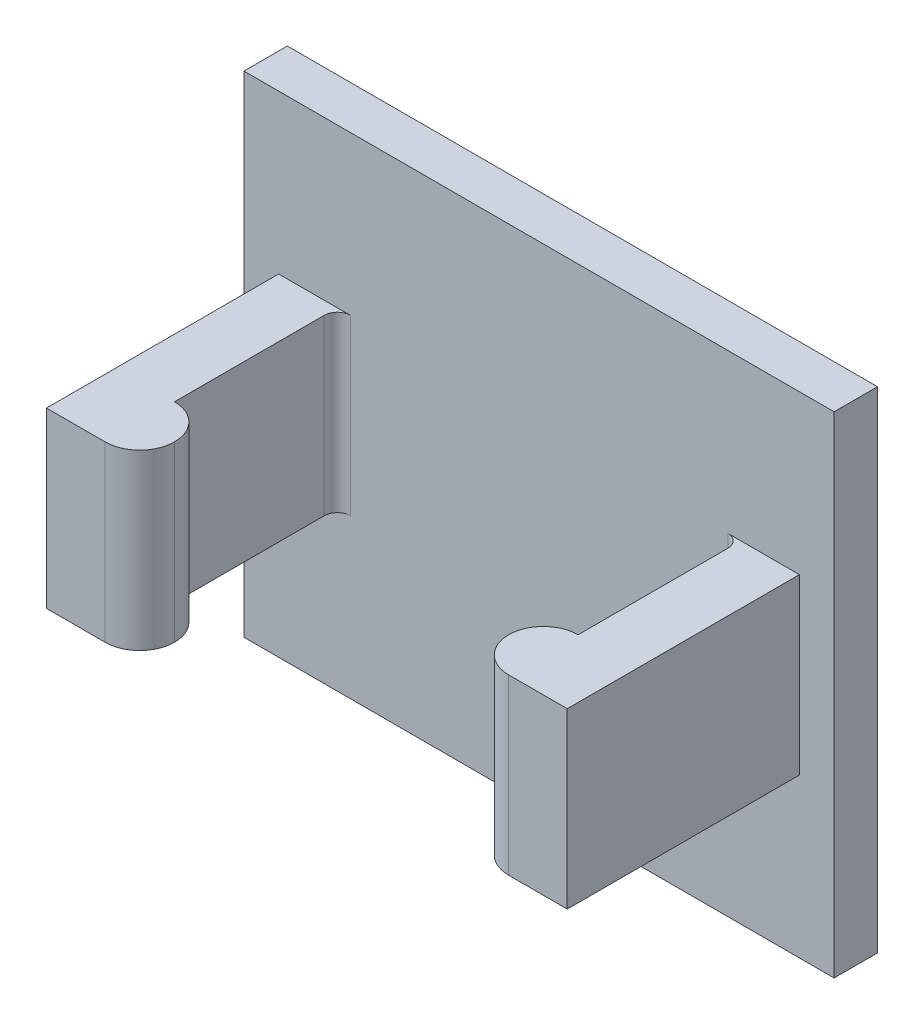
SolidWorks part; units mm, degrees
ref_plane "정면" through (0, 0, 0) normal (0, 0, 1) x (1, 0, 0)
ref_plane "윗면" through (0, 0, 0) normal (0, 1, 0) x (1, 0, 0)
ref_plane "우측면" through (0, 0, 0) normal (1, 0, 0) x (0, 0, -1)
sketch "스케치1" plane through (0, 0, 0) normal (0, 0, 1) x (1, 0, 0)
  line L1 (-6, -5.65) -> (6, -5.65)
  line L2 (-6, -5.65) -> (-6, 5.65)
  line L3 (-6, 5.65) -> (6, 5.65)
  line L4 (6, -5.65) -> (6, 5.65)
  line L5 (-6, -5.65) -> (6, 5.65) construction
  line L6 (-6, 5.65) -> (6, -5.65) construction
  point P0 (0, 0)
  dimension "D1" = 12
  dimension "D2" = 11.3
extrude "보스-돌출1" add sketch "스케치1" along normal blind 1
sketch "스케치2" plane through (0, 0, 1) normal (0, 0, 1) x (1, 0, 0)
  line L0 (-6, 5.65) -> (-6, -5.65) construction
  line L1 (-6, 2) -> (-4.65, 2)
  line L2 (-6, 2) -> (-6, -2)
  line L3 (-6, -2) -> (-4.65, -2)
  line L4 (-4.65, 2) -> (-4.65, -2)
  line L5 (6, -5.65) -> (6, 5.65) construction
  line L6 (6, 2) -> (4.65, 2)
  line L7 (6, 2) -> (6, -2)
  line L8 (6, -2) -> (4.65, -2)
  line L9 (4.65, 2) -> (4.65, -2)
  point P12 (-4.65, 0)
  point P14 (6, 0)
  dimension "D1" = 1.35
  dimension "D2" = 1.35
  dimension "D3" = 4
  dimension "D4" = 4
  dimension "D5" = 0
  dimension "D6" = 0
extrude "보스-돌출2" add sketch "스케치2" along normal blind 5.35
sketch "스케치3" plane through (-4.65, 0, 0) normal (1, 0, 0) x (0, 0, -1)
  line L0 (-6.35, -2) -> (-1, -2) construction
  line L1 (-6.35, 2) -> (-4.75, 2)
  line L2 (-6.35, 2) -> (-6.35, -2)
  line L3 (-6.35, -2) -> (-4.75, -2)
  line L4 (-4.75, 2) -> (-4.75, -2)
  dimension "D1" = 1.6
extrude "보스-돌출3" add sketch "스케치3" along normal blind 0.8
sketch "스케치4" plane through (4.65, 0, 0) normal (-1, 0, 0) x (0, 0, 1)
  line L0 (6.35, -2) -> (1, -2) construction
  line L1 (6.35, 2) -> (4.75, 2)
  line L2 (6.35, 2) -> (6.35, -2)
  line L3 (6.35, -2) -> (4.75, -2)
  line L4 (4.75, 2) -> (4.75, -2)
  dimension "D1" = 1.6
extrude "보스-돌출4" add sketch "스케치4" along normal blind 0.8
fillet "필렛1" radius 0.8 4 edges at (3.85, 0, 6.35) (3.85, 0, 4.75) (-3.85, 0, 6.35) (-3.85, 0, 4.75)
fillet "필렛2" radius 0.3 2 edges at (4.65, 0, 1) (-4.65, 0, 1)
sketch "스케치5" plane through (-6, 0, 0) normal (-1, 0, 0) x (0, 0, 1)
  line L1 (0, 5.65) -> (1, 5.65)
  line L2 (0, 5.65) -> (0, -5.65)
  line L3 (0, -5.65) -> (1, -5.65)
  line L4 (1, 5.65) -> (1, -5.65)
extrude "보스-돌출5" add sketch "스케치5" along normal blind 0.8
sketch "스케치6" plane through (6, 0, 0) normal (1, 0, 0) x (0, 0, -1)
  line L1 (-1, 5.65) -> (0, 5.65)
  line L2 (-1, 5.65) -> (-1, -5.65)
  line L3 (-1, -5.65) -> (0, -5.65)
  line L4 (0, 5.65) -> (0, -5.65)
extrude "보스-돌출6" add sketch "스케치6" along normal blind 0.8
